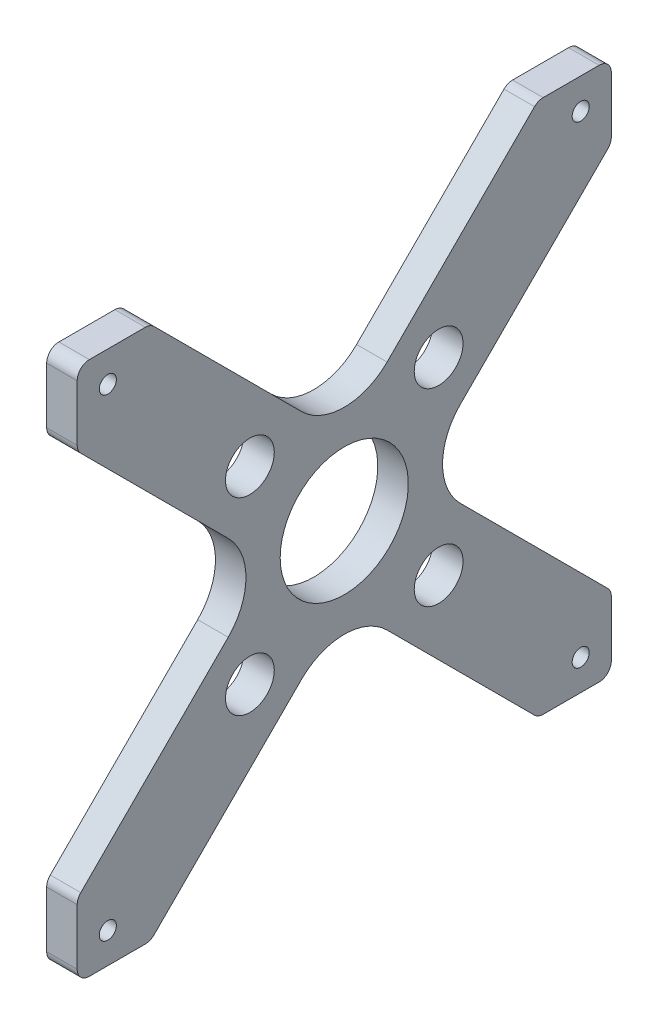
SolidWorks part; units mm, degrees
ref_plane "Front Plane" through (0, 0, 0) normal (0, 0, 1) x (1, 0, 0)
ref_plane "Top Plane" through (0, 0, 0) normal (0, 1, 0) x (1, 0, 0)
ref_plane "Right Plane" through (0, 0, 0) normal (1, 0, 0) x (0, 0, -1)
sketch "Sketch1" plane through (0, 0, 0) normal (1, 0, 0) x (0, 0, -1)
  line L0 (-53.8748, 46.8252) -> (57.2929, -64.3425) construction
  line L1 (57.2929, 46.8252) -> (-53.8748, -64.3425) construction
  line L2 (-53.8748, 46.8252) -> (-38.6348, 46.8252)
  line L3 (-53.8748, 46.8252) -> (-53.8748, 31.5852)
  line L4 (57.2929, 46.8252) -> (57.2929, 31.5852)
  line L5 (57.2929, 46.8252) -> (42.0529, 46.8252)
  line L6 (57.2929, -64.3425) -> (42.0529, -64.3425)
  line L7 (57.2929, -64.3425) -> (57.2929, -49.1025)
  line L8 (-53.8748, -64.3425) -> (-53.8748, -49.1025)
  line L9 (-53.8748, -64.3425) -> (-38.6348, -64.3425)
  line L10 (-53.8748, 31.5852) -> (42.0529, -64.3425) construction
  line L11 (-38.6348, 46.8252) -> (57.2929, -49.1025) construction
  line L12 (42.0529, 46.8252) -> (-53.8748, -49.1025) construction
  line L13 (57.2929, 31.5852) -> (-38.6348, -64.3425) construction
  line L14 (-38.6348, 46.8252) -> (-7.2039, 15.3943)
  line L15 (42.0529, 46.8252) -> (10.622, 15.3943)
  line L16 (57.2929, 31.5852) -> (25.862, 0.1543)
  line L17 (57.2929, -49.1025) -> (25.862, -17.6716)
  line L18 (42.0529, -64.3425) -> (10.622, -32.9116)
  line L19 (-38.6348, -64.3425) -> (-7.2039, -32.9116)
  line L20 (-53.8748, -49.1025) -> (-22.4439, -17.6716)
  line L21 (-53.8748, 31.5852) -> (-22.4439, 0.1543)
  circle A0 centre (1.709, -8.7587) radius 6.2063 construction
  arc A1 (-7.2039, 15.3943) -> (10.622, 15.3943) centre (1.709, 24.3073) ccw
  arc A2 (25.862, 0.1543) -> (25.862, -17.6716) centre (34.7749, -8.7587) ccw
  arc A3 (10.622, -32.9116) -> (-7.2039, -32.9116) centre (1.709, -41.8246) ccw
  arc A4 (-22.4439, -17.6716) -> (-22.4439, 0.1543) centre (-31.3569, -8.7587) ccw
  circle A5 centre (-47.5035, 40.4538) radius 1.778
  circle A6 centre (50.9215, 40.4538) radius 1.778
  circle A7 centre (50.9215, -57.9712) radius 1.778
  circle A8 centre (-47.5035, -57.9712) radius 1.778
  circle A9 centre (1.709, -8.7587) radius 13.335
  point P20 (1.709, -8.7587)
  point P38 (1.709, -8.7587)
extrude "Boss-Extrude1" add sketch "Sketch1" along normal blind 6.35 contours L21 A4 L20 L8 L9 L19 A3 L18 L6 L7 L17 A2 L16 L4 L5 L15 A1 L14 L2 L3
extrude "Cut-Extrude1" cut sketch "Sketch1<9>" along normal blind 11.938 contours A9
sketch "Sketch1<9>" plane through (0, 0, 0) normal (1, 0, 0) x (0, 0, -1) same geometry as "Sketch1"
extrude "Cut-Extrude2" cut sketch "Sketch1<10>" along normal blind 24.638 contours A8
sketch "Sketch1<10>" plane through (0, 0, 0) normal (1, 0, 0) x (0, 0, -1) same geometry as "Sketch1"
extrude "Cut-Extrude3" cut sketch "Sketch1<11>" along normal blind 24.13 contours A7
sketch "Sketch1<11>" plane through (0, 0, 0) normal (1, 0, 0) x (0, 0, -1) same geometry as "Sketch1"
extrude "Cut-Extrude4" cut sketch "Sketch1<12>" along normal blind 38.862 contours A6
sketch "Sketch1<12>" plane through (0, 0, 0) normal (1, 0, 0) x (0, 0, -1) same geometry as "Sketch1"
extrude "Cut-Extrude5" cut sketch "Sketch1<13>" along normal blind 13.462 contours A5
sketch "Sketch1<13>" plane through (0, 0, 0) normal (1, 0, 0) x (0, 0, -1) same geometry as "Sketch1"
fillet "Fillet1" radius 2.54 12 edges at (3.175, 31.5852, -57.2929) (3.175, 46.8252, -42.0529) (3.175, 46.8252, -57.2929) (3.175, 31.5852, 53.8748) (3.175, 46.8252, 53.8748) (3.175, 46.8252, 38.6348) (3.175, -64.3425, 38.6348) (3.175, -49.1025, 53.8748) (3.175, -64.3425, 53.8748) (3.175, -64.3425, -42.0529) (3.175, -64.3425, -57.2929) (3.175, -49.1025, -57.2929)
sketch "Sketch2" plane through (0, 0, 0) normal (-1, 0, 0) x (0, 0, 1)
  line L0 (-28.9714, 3.2638) -> (-13.7314, 18.5038) construction
  line L1 (-56.5489, 30.8413) -> (-25.862, 0.1543) construction
  line L2 (-41.3089, 46.0813) -> (-10.622, 15.3943) construction
  circle A0 centre (-21.3514, 10.8838) radius 5.08
  point P8 (0, 0)
  point P17 (0, -8.7587)
  dimension "D1" = 10.16
extrude "Cut-Extrude6" cut sketch "Sketch2" against normal blind 13.462
ref_plane "Plane1" through (0, -8.7587, 0) normal (0, 1, 0) x (1, 0, 0)
mirror "Mirror1" about plane through (0, -8.7587, 0) normal (0, 1, 0) of "Cut-Extrude6"
ref_plane "Plane2" through (0, 0, -1.709) normal (0, 0, 1) x (1, 0, 0)
mirror "Mirror2" about plane through (0, 0, -1.709) normal (0, 0, 1) of "Mirror1", "Cut-Extrude6"
